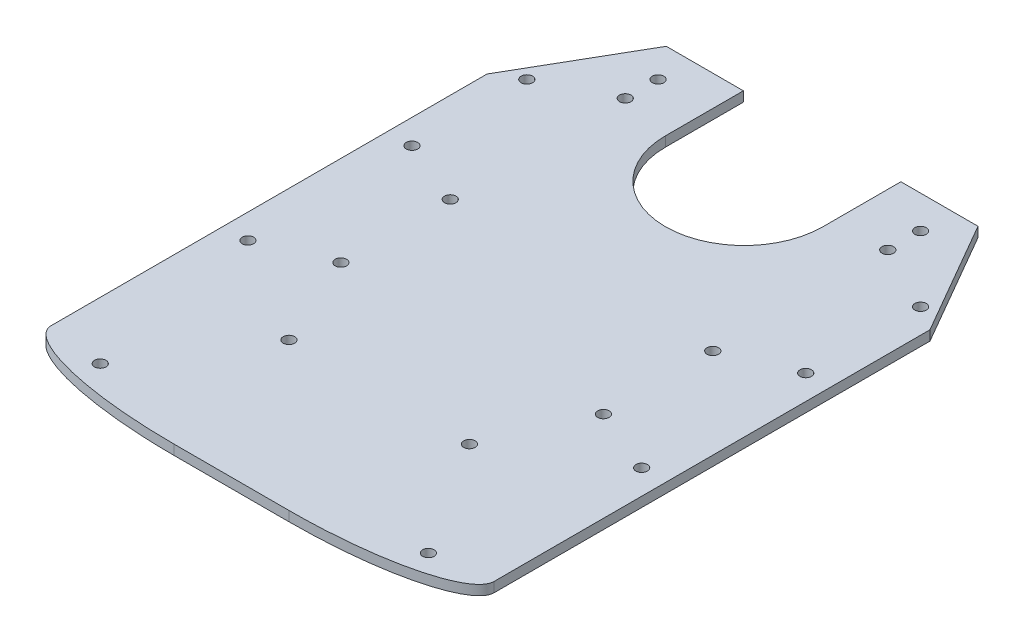
SolidWorks part; units mm, degrees
material "Balsa"
ref_plane "Alzado" through (0, 0, 0) normal (0, 0, 1) x (1, 0, 0)
ref_plane "Planta" through (0, 0, 0) normal (0, 1, 0) x (1, 0, 0)
ref_plane "Vista lateral" through (0, 0, 0) normal (1, 0, 0) x (0, 0, -1)
sketch "Sketch2" plane through (0, 0, 0) normal (0, 1, 0) x (1, 0, 0)
  line L1 (-67.5, 90) -> (67.5, 90)
  line L2 (-67.5, 90) -> (-67.5, -90)
  line L3 (-67.5, -90) -> (67.5, -90)
  line L4 (67.5, 90) -> (67.5, -90)
  line L5 (-67.5, 90) -> (67.5, -90) construction
  line L6 (-67.5, -90) -> (67.5, 90) construction
  point P0 (0, 0)
  dimension "D1" = 135
  dimension "D2" = 180
extrude "Boss-Extrude2" add sketch "Sketch2" along normal blind 3
sketch "Sketch3" plane through (0, 3, 0) normal (0, 1, 0) x (1, 0, 0)
  line L0 (0, -90) -> (0, 90) construction
  line L1 (-67.5, -90) -> (67.5, -90) construction
  line L2 (67.5, 90) -> (-67.5, 90) construction
  line L3 (-67.5, 90) -> (-67.5, -90) construction
  line L4 (-67.5, -90) -> (67.5, -90) construction
  circle A0 centre (-27.5, -45) radius 1.75
  circle A1 centre (27.5, -45) radius 1.75
  circle A2 centre (-50, -80) radius 1.75
  circle A3 centre (50, -80) radius 1.75
  dimension "D1" = 40
  dimension "D3" = 3.5
  dimension "D4" = 10
  dimension "D2" = 45
  dimension "D5" = 50
extrude "Cut-Extrude1" cut sketch "Sketch3" against normal through all
fillet "Fillet1" radius 12.5 1 edges at (-67.5, 1.5, 90) second distance 50 first distance on face at (-67.5, 1.5, 0)
fillet "Fillet2" radius 12.5 1 edges at (67.5, 1.5, 90) second distance 50 first distance on face at (67.5, 1.5, 0)
chamfer "Chamfer2" distance 20 angle 60 1 edges at (67.5, 1.5, -90) first distance on face at (0, 1.5, -90)
chamfer "Chamfer3" distance 20 angle 60 1 edges at (-67.5, 1.5, -90) first distance on face at (-10, 1.5, -90)
sketch "Sketch4" plane through (0, 3, 0) normal (0, 1, 0) x (1, 0, 0)
  line L0 (0, 90) -> (0, 0) construction
  line L1 (47.5, 90) -> (-47.5, 90) construction
  circle A0 centre (-40, 80) radius 1.75
  circle A1 centre (-60, 60) radius 1.75
  circle A2 centre (60, 60) radius 1.75
  circle A3 centre (40, 80) radius 1.75
  dimension "D1" = 3.5
  dimension "D2" = 10
  dimension "D3" = 30
  dimension "D4" = 40
  dimension "D5" = 60
extrude "Cut-Extrude2" cut sketch "Sketch4" against normal through all
sketch "Sketch5" plane through (0, 3, 0) normal (0, 1, 0) x (1, 0, 0)
  line L0 (0, 90) -> (0, -90) construction
  line L1 (47.5, 90) -> (-47.5, 90) construction
  line L2 (-17.5, -90) -> (17.5, -90) construction
  circle A0 centre (-40, 70) radius 1.75
  circle A1 centre (40, 70) radius 1.75
  dimension "D1" = 20
  dimension "D3" = 3.5
  dimension "D2" = 40
extrude "Cut-Extrude3" cut sketch "Sketch5" against normal through all
sketch "Sketch6" plane through (0, 3, 0) normal (0, 1, 0) x (1, 0, 0)
  line L0 (0, 90) -> (0, -90) construction
  line L5 (47.5, 90) -> (-47.5, 90) construction
  line L6 (-17.5, -90) -> (17.5, -90) construction
  line L7 (-67.5, 0) -> (67.5, 0) construction
  line L8 (-67.5, 55.359) -> (-67.5, -77.5) construction
  line L9 (67.5, -77.5) -> (67.5, 55.359) construction
  line L11 (-60, 25) -> (60, 25) construction
  line L12 (-60, 25) -> (-60, -25) construction
  line L13 (-60, -25) -> (60, -25) construction
  line L14 (60, 25) -> (60, -25) construction
  line L15 (-60, 25) -> (60, -25) construction
  line L16 (-60, -25) -> (60, 25) construction
  circle A0 centre (-60, 25) radius 1.75
  circle A1 centre (60, 25) radius 1.75
  circle A2 centre (60, -25) radius 1.75
  circle A3 centre (-60, -25) radius 1.75
  circle A4 centre (-40, 16.6667) radius 1.75
  circle A5 centre (40, 16.6667) radius 1.75
  circle A6 centre (40, -16.6667) radius 1.75
  circle A7 centre (-40, -16.6667) radius 1.75
  point P5 (0, 0)
  point P14 (0, 0)
  dimension "D1" = 3.5
  dimension "D2" = 120
  dimension "D3" = 50
  dimension "D4" = 40
extrude "Cut-Extrude4" cut sketch "Sketch6" against normal through all
sketch "Sketch7" plane through (0, 3, 0) normal (0, 1, 0) x (1, 0, 0)
  line L0 (47.5, 90) -> (-47.5, 90) construction
  line L1 (24, 66.25) -> (24, 90)
  line L2 (24, 90) -> (-24, 90)
  line L3 (-24, 90) -> (-24, 66.25)
  arc A0 (-24, 66.25) -> (24, 66.25) centre (0, 66.25) ccw
  dimension "D2" = 48
  dimension "D1" = 23.75
extrude "Cut-Extrude5" cut sketch "Sketch7" against normal through all
